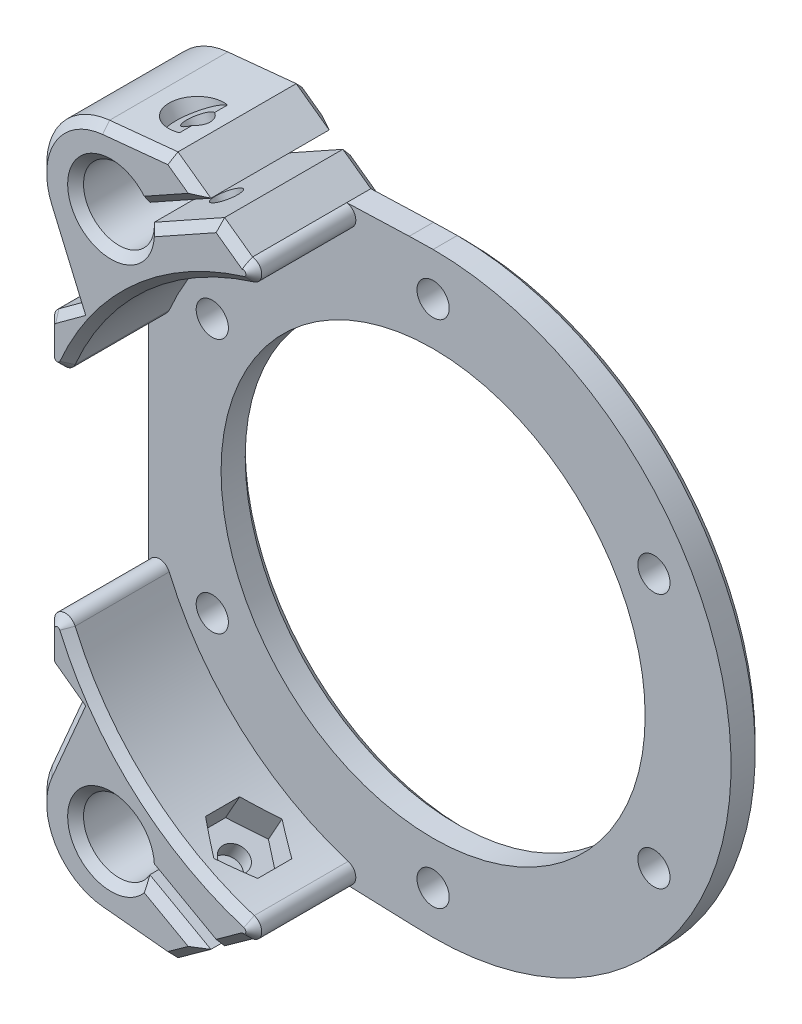
SolidWorks part; units mm, degrees
ref_plane "Front Plane" through (0, 0, 0) normal (0, 0, 1) x (1, 0, 0)
ref_plane "Top Plane" through (0, 0, 0) normal (0, 1, 0) x (1, 0, 0)
ref_plane "Right Plane" through (0, 0, 0) normal (1, 0, 0) x (0, 0, -1)
sketch "Sketch1" plane through (0, 0, 0) normal (0, 0, 1) x (1, 0, 0)
  line L0 (0, 36.75) -> (-10, 33.3337)
  line L1 (-10, 33.3337) -> (-15, 29)
  line L2 (-15, 29) -> (-58.05, 27.5)
  line L3 (-58.05, 27.5) -> (-76.5, 14)
  line L4 (-76.5, 14) -> (-76.5, -14)
  line L5 (-87.0431, 0) -> (20.0163, 0) construction
  line L6 (0, 32.2788) -> (0, 0) construction
  line L7 (76.5, 14) -> (76.5, -14)
  line L8 (58.05, 27.5) -> (76.5, 14)
  line L9 (15, 29) -> (58.05, 27.5)
  line L10 (10, 33.3337) -> (15, 29)
  line L11 (0, 36.75) -> (10, 33.3337)
  line L12 (0, -36.75) -> (10, -33.3337)
  line L13 (10, -33.3337) -> (15, -29)
  line L14 (15, -29) -> (58.05, -27.5)
  line L15 (58.05, -27.5) -> (76.5, -14)
  line L16 (-58.05, -27.5) -> (-76.5, -14)
  line L17 (-15, -29) -> (-58.05, -27.5)
  line L18 (-10, -33.3337) -> (-15, -29)
  line L19 (0, -36.75) -> (-10, -33.3337)
  circle A0 centre (0, 30) radius 3
  circle A1 centre (-50, 0) radius 19.75
  circle A2 centre (50, 0) radius 19.75
  circle A3 centre (0, -30) radius 3
  point P35 (76.5, 0)
  point P36 (-76.5, 0)
  dimension "D1" = 6
  dimension "D2" = 39.5
  dimension "D3" = 60
  dimension "D4" = 100
  dimension "D5" = 153
  dimension "D6" = 73.5
  dimension "D7" = 28
  dimension "D8" = 55
  dimension "D9" = 18.45
  dimension "D10" = 30
  dimension "D11" = 20
  dimension "D12" = 58
extrude "Boss-Extrude1" add sketch "Sketch1" along normal blind 3
sketch "Sketch2" plane through (0, 0, 3) normal (0, 0, 1) x (1, 0, 0)
  line L1 (8.5, 20) -> (-8.5, 20)
  line L2 (12.5, 16) -> (12.5, -16)
  line L3 (8.5, -20) -> (-8.5, -20)
  line L4 (-12.5, 16) -> (-12.5, -16)
  line L5 (12.5, 20) -> (-12.5, -20) construction
  line L6 (12.5, -20) -> (-12.5, 20) construction
  arc A1 (8.5, 20) -> (12.5, 16) centre (8.5, 16) cw
  arc A2 (12.5, -16) -> (8.5, -20) centre (8.5, -16) cw
  arc A3 (-8.5, -20) -> (-12.5, -16) centre (-8.5, -16) cw
  arc A4 (-8.5, 20) -> (-12.5, 16) centre (-8.5, 16) ccw
  point P0 (0, 0)
  dimension "D1" = 4
  dimension "D2" = 25
  dimension "D3" = 40
extrude "Cut-Extrude1" cut sketch "Sketch2" against normal through all
sketch "Sketch3" plane through (0, 0, 3) normal (0, 0, 1) x (1, 0, 0)
  line L0 (-58.05, 27.5) -> (-65, 32.5)
  line L1 (-58.05, 27.5) -> (-76.5, 14) construction
  line L2 (-65, 32.5) -> (-80.2046, 31)
  line L3 (-80.2046, 31) -> (-73.7667, 16)
  line L4 (-73.7667, 16) -> (-58.05, 27.5)
  line L5 (0, 0) -> (0, 46.5274) construction
  line L6 (73.7667, 16) -> (58.05, 27.5)
  line L7 (80.2046, 31) -> (73.7667, 16)
  line L8 (65, 32.5) -> (80.2046, 31)
  line L9 (58.05, 27.5) -> (65, 32.5)
  line L10 (0, 0) -> (-26.0239, 0) construction
  line L11 (58.05, -27.5) -> (65, -32.5)
  line L12 (65, -32.5) -> (80.2046, -31)
  line L13 (80.2046, -31) -> (73.7667, -16)
  line L14 (73.7667, -16) -> (58.05, -27.5)
  line L15 (-73.7667, -16) -> (-58.05, -27.5)
  line L16 (-80.2046, -31) -> (-73.7667, -16)
  line L17 (-65, -32.5) -> (-80.2046, -31)
  line L18 (-58.05, -27.5) -> (-65, -32.5)
  line L19 (-15, 29) -> (-58.05, 27.5) construction
  circle A0 centre (-70.5, 25.5) radius 3.3
  circle A1 centre (70.5, 25.5) radius 3.3
  circle A2 centre (-70.5, -25.5) radius 3.3
  circle A3 centre (70.5, -25.5) radius 3.3
  dimension "D1" = 6.6
  dimension "D2" = 70.5
  dimension "D3" = 25.5
  dimension "D4" = 62
  dimension "D5" = 65
  dimension "D6" = 32
  dimension "D7" = 80.2046
  dimension "D8" = 65
extrude "Boss-Extrude2" add sketch "Sketch3" against normal up to surface (3 mm away) up to face at (0, 0, 0)
fillet "Fillet1" radius 6.5 4 edges at (-80.2046, 31, 1.5) (-80.2046, -31, 1.5) (80.2046, -31, 1.5) (80.2046, 31, 1.5)
sketch "Sketch4" plane through (0, 0, 3) normal (0, 0, 1) x (1, 0, 0)
  line L0 (0, 48.5627) -> (0, -47.8194) construction
  circle A0 centre (-50, 0) radius 23.75 construction
  circle A1 centre (-50, 23.75) radius 1.5
  circle A2 centre (-70.5681, 11.875) radius 1.5
  circle A3 centre (-70.5681, -11.875) radius 1.5
  circle A4 centre (-50, -23.75) radius 1.5
  circle A5 centre (-29.4319, -11.875) radius 1.5
  circle A6 centre (-29.4319, 11.875) radius 1.5
  circle A7 centre (29.4319, 11.875) radius 1.5
  circle A8 centre (29.4319, -11.875) radius 1.5
  circle A9 centre (50, -23.75) radius 1.5
  circle A10 centre (70.5681, -11.875) radius 1.5
  circle A11 centre (70.5681, 11.875) radius 1.5
  circle A12 centre (50, 23.75) radius 1.5
  point P21 (-50, 0)
  point P31 (50, 0)
  dimension "D1" = 47.5
  dimension "D3" = 3
  dimension "D2" = 6
extrude "Cut-Extrude2" cut sketch "Sketch4" against normal through all
sketch "Sketch5" plane through (0, 0, 3) normal (0, 0, 1) x (1, 0, 0)
  line L12 (-57.9916, 27.5812) -> (-50, 27.75)
  line L13 (-76.5591, 14.0807) -> (-76.5, 0)
  line L14 (-76.5, 14) -> (-76.5, -14) construction
  line L15 (-84.5459, 0) -> (89.0041, 0) construction
  line L16 (-73.89, 16.0337) -> (-76.5591, 14.0807)
  line L17 (-76.7941, 22.8002) -> (-73.89, 16.0337)
  line L18 (-64.9722, 32.6032) -> (-71.3771, 31.9714)
  line L19 (-57.9916, 27.5812) -> (-64.9722, 32.6032)
  line L20 (-73.89, 16.0337) -> (-76.5591, 14.0807)
  line L21 (-76.7941, 22.8002) -> (-73.89, 16.0337)
  line L22 (-64.9722, 32.6032) -> (-71.3771, 31.9714)
  line L23 (-57.9916, 27.5812) -> (-64.9722, 32.6032)
  line L24 (-57.9916, -27.5812) -> (-64.9722, -32.6032)
  line L25 (-64.9722, -32.6032) -> (-71.3771, -31.9714)
  line L26 (-76.7941, -22.8002) -> (-73.89, -16.0337)
  line L27 (-73.89, -16.0337) -> (-76.5591, -14.0807)
  line L28 (-76.5591, -14.0807) -> (-76.5, 0)
  line L29 (-57.9916, -27.5812) -> (-50, -27.75)
  line L31 (-98.6251, 56.8967) -> (99.3355, 56.8967)
  line L32 (-98.6251, 56.8967) -> (-98.6251, -48.9335)
  line L33 (-98.6251, -48.9335) -> (99.3355, -48.9335)
  line L34 (99.3355, 56.8967) -> (99.3355, -48.9335)
  arc A0 (-50, -27.75) -> (-50, 27.75) centre (-50, 0) ccw
  arc A4 (-71.3771, -31.9714) -> (-76.7941, -22.8002) centre (-70.7291, -25.4032) cw
  arc A5 (-71.3771, 31.9714) -> (-76.7941, 22.8002) centre (-70.7291, 25.4032) ccw
  arc A6 (-71.3771, 31.9714) -> (-76.7941, 22.8002) centre (-70.7291, 25.4032) ccw
  dimension "D1" = 55.5
  dimension "D2" = 0.1
extrude "Cut-Extrude3" cut sketch "Sketch5" against normal through all
sketch "Sketch6" plane through (0, 0, 3) normal (0, 0, 1) x (1, 0, 0)
  line L0 (-76.7022, 22.8396) -> (-73.7667, 16)
  line L1 (-76.7022, 22.8396) -> (-73.7667, 16) construction
  line L2 (-71.3673, 31.8718) -> (-65, 32.5)
  line L3 (-65, 32.5) -> (-58.05, 27.5)
  line L4 (-58.05, 27.5) -> (-50, 26.75)
  line L5 (-76.5, 14) -> (-73.7667, 16)
  line L6 (-76.5, 14) -> (-76.5, 3.6486)
  line L7 (-76.5, 14) -> (-76.5, -14) construction
  line L8 (-50, 0) -> (-84.0522, 0) construction
  line L9 (-76.5, -14) -> (-76.5, -3.6486)
  line L10 (-76.5, -14) -> (-73.7667, -16)
  line L11 (-58.05, -27.5) -> (-50, -26.75)
  line L12 (-65, -32.5) -> (-58.05, -27.5)
  line L13 (-71.3673, -31.8718) -> (-65, -32.5)
  line L14 (-76.7022, -22.8396) -> (-73.7667, -16)
  arc A0 (-50, 26.75) -> (-76.5, 3.6486) centre (-50, 0) ccw
  arc A1 (-76.7022, 22.8396) -> (-71.3673, 31.8718) centre (-70.7291, 25.4032) cw
  arc A2 (-76.7022, -22.8396) -> (-71.3673, -31.8718) centre (-70.7291, -25.4032) ccw
  arc A3 (-50, -26.75) -> (-76.5, -3.6486) centre (-50, 0) cw
  circle A4 centre (-70.5, 25.5) radius 3.3
  circle A5 centre (-70.5, 25.5) radius 3.3 construction
  circle A6 centre (-70.5, -25.5) radius 3.3
  dimension "D1" = 53.5
extrude "Boss-Extrude3" add sketch "Sketch6" along normal blind 9.5
fillet "Fillet2" radius 1 6 edges at (-50, -26.75, 7.75) (-76.5, -3.6486, 7.75) (-50, 26.75, 7.75) (-76.5, 3.6486, 7.75) (-76.5, -14, 6.25) (-76.5, 14, 6.25)
sketch "Sketch7" plane through (0, 0, 12.5) normal (0, 0, 1) x (1, 0, 0)
  line L0 (-68.7299, 26.5013) -> (-57.4519, 32.7968)
  line L1 (-57.4519, 32.7968) -> (-56.7571, 31.5522)
  line L2 (-56.7571, 31.5522) -> (-67.9885, 25.2827)
  line L3 (-67.9885, 25.2827) -> (-68.7299, 26.5013)
  line L4 (-70.5, 25.5) -> (-59.611, 31.5783) construction
  line L5 (-50, 0) -> (-95.3725, 0) construction
  line L6 (-70.5, -25.5) -> (-59.611, -31.5783) construction
  line L7 (-67.9885, -25.2827) -> (-68.7299, -26.5013)
  line L8 (-56.7571, -31.5522) -> (-67.9885, -25.2827)
  line L9 (-57.4519, -32.7968) -> (-56.7571, -31.5522)
  line L10 (-68.7299, -26.5013) -> (-57.4519, -32.7968)
extrude "Cut-Extrude4" cut sketch "Sketch7" against normal through all
sketch "Sketch8" plane through (-26.9121, 48.2118, 0) normal (-0.4874, 0.8732, 0) x (0.8732, 0.4874, 0)
  line L0 (-25.9438, -3) -> (-25.9438, -12.5) construction
  line L1 (-57.1843, -3) -> (-15.9087, -3) construction
  line L2 (-36.8959, -12.5) -> (-21.1915, -12.5) construction
  circle A0 centre (-43.0415, -7.75) radius 1.2
  point P10 (-25.9438, -12.5)
  point P11 (-25.9438, -7.75)
  dimension "D1" = 2.4
extrude "Cut-Extrude5" cut sketch "Sketch8" against normal blind 18 from offset 10
sketch "Sketch9" plane through (-26.9121, 48.2118, 0) normal (-0.4874, 0.8732, 0) x (0.8732, 0.4874, 0)
  circle A0 centre (-43.0415, -7.75) radius 2.325
  dimension "D1" = 4.65
extrude "Cut-Extrude6" cut sketch "Sketch9" against normal blind 4.5 from offset 10
sketch "Sketch10" plane through (-26.9121, 48.2118, 0) normal (-0.4874, 0.8732, 0) x (0.8732, 0.4874, 0)
  line L1 (-43.0415, -4.5746) -> (-45.7915, -6.1623)
  line L2 (-45.7915, -6.1623) -> (-45.7915, -9.3377)
  line L3 (-45.7915, -9.3377) -> (-43.0415, -10.9254)
  line L4 (-43.0415, -10.9254) -> (-40.2915, -9.3377)
  line L5 (-40.2915, -9.3377) -> (-40.2915, -6.1623)
  line L6 (-40.2915, -6.1623) -> (-43.0415, -4.5746)
  circle A0 centre (-43.0415, -7.75) radius 2.75 construction
  dimension "D1" = 5.5
extrude "Cut-Extrude7" cut sketch "Sketch10" along normal blind 3.5 from offset 5 offset against normal yes
mirror "Mirror1" about plane through (0, 0, 0) normal (0, 1, 0) of "Cut-Extrude7", "Cut-Extrude6", "Cut-Extrude5"
chamfer "Chamfer1" distance 0.75 angle 45 33 edges at (-27.9319, 11.875, 0) (-27.9319, -11.875, 0) (-48.5, -23.75, 0) (-69.0681, -11.875, 0) (-69.0681, 11.875, 0) (-48.5, 23.75, 0) (-30.25, 0, 0) (-63.4672, 31.3973, 0) (-68.1836, 32.1859, 0) (-76.3257, 28.7089, 0) (-75.2344, 19.4198, 0) (-74.9286, 15.1498, 0) (-76.3918, 13.9451, 0) (-76.5, 0, 0) (-76.3918, -13.9451, 0) (-74.9286, -15.1498, 0) (-75.2344, -19.4198, 0) (-76.3257, -28.7089, 0) (-68.1836, -32.1859, 0) (-63.4672, -31.3973, 0) (-64.7793, -28.7066, 0) (-73.6627, -24.558, 0) (-63.932, -27.5471, 0) (-59.3534, -28.4377, 0) (-55.1362, -27.6015, 0) (-51.1112, -27.7265, 0) (-22.25, 0, 0) (-51.1112, 27.7265, 0) (-55.1362, 27.6015, 0) (-59.3534, 28.4377, 0) (-63.932, 27.5471, 0) (-73.6627, 24.558, 0) (-64.7793, 28.7066, 0)
chamfer "Chamfer2" distance 0.74 angle 45 28 edges at (-63.4672, -31.3973, 12.5) (-64.7793, -28.7066, 12.5) (-59.3534, -28.4377, 12.5) (-63.932, -27.5471, 12.5) (-73.6627, -24.558, 12.5) (-68.1836, -32.1859, 12.5) (-57.2017, -26.5863, 12.5) (-76.3257, -28.7089, 12.5) (-75.2344, -19.4198, 12.5) (-74.9286, -15.1498, 12.5) (-76.3918, -13.9451, 12.5) (-76.5, -12.2192, 12.5) (-75.7013, -9.9664, 12.5) (-67.8912, -19.8864, 12.5) (-74.9286, 15.1498, 12.5) (-76.3918, 13.9451, 12.5) (-75.2344, 19.4198, 12.5) (-76.5, 12.2192, 12.5) (-76.3257, 28.7089, 12.5) (-75.7013, 9.9664, 12.5) (-68.1836, 32.1859, 12.5) (-63.4672, 31.3973, 12.5) (-64.7793, 28.7066, 12.5) (-73.6627, 24.558, 12.5) (-63.932, 27.5471, 12.5) (-59.3534, 28.4377, 12.5) (-57.2017, 26.5863, 12.5) (-67.8912, 19.8864, 12.5)
